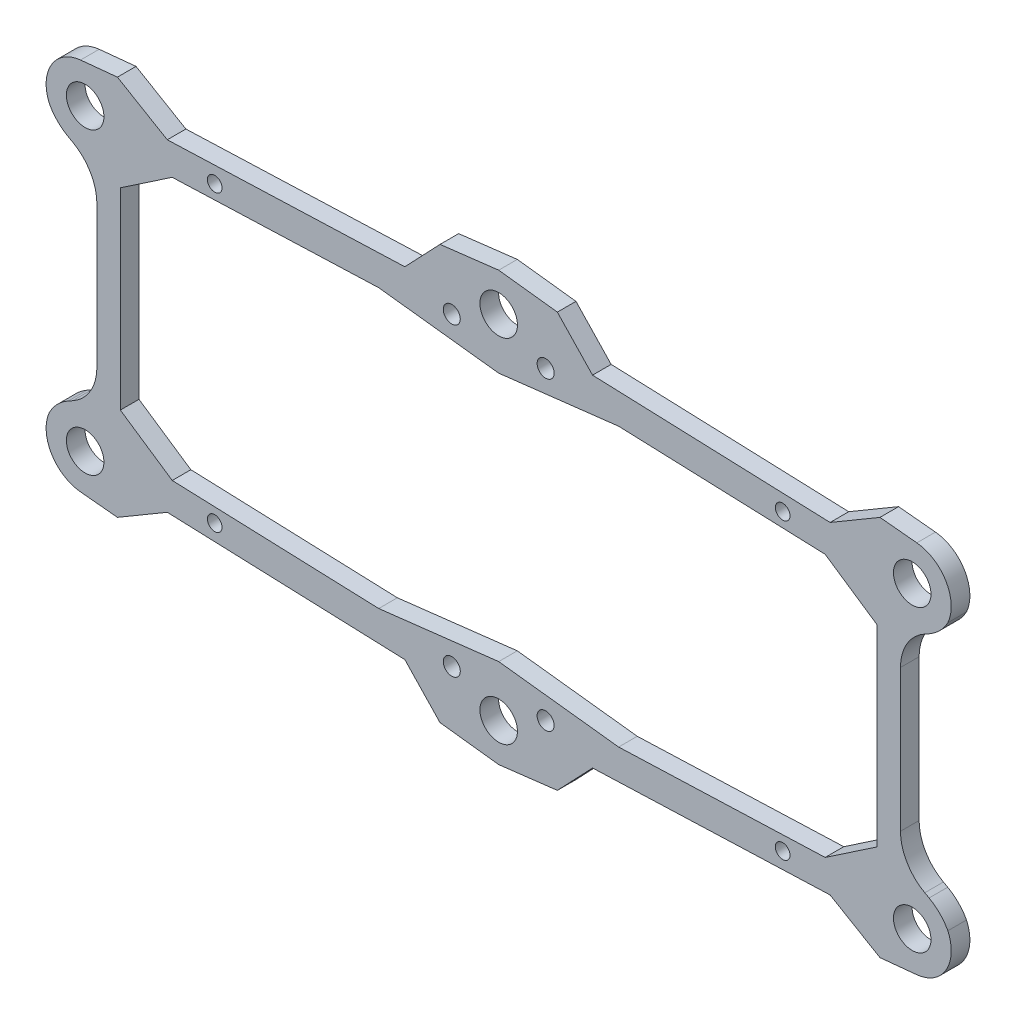
SolidWorks part; units mm, degrees
material "AISI 304"
ref_plane "Front Plane" through (0, 0, 0) normal (0, 0, 1) x (1, 0, 0)
ref_plane "Top Plane" through (0, 0, 0) normal (0, 1, 0) x (1, 0, 0)
ref_plane "Right Plane" through (0, 0, 0) normal (1, 0, 0) x (0, 0, -1)
sketch "Sketch1" plane through (0, 0, 0) normal (0, 0, 1) x (1, 0, 0)
  line L0 (0, 36.5) -> (-10, 35.3071)
  line L1 (-10, 35.3071) -> (-16, 29)
  line L2 (-16, 29) -> (-56.5, 27.5)
  line L3 (-56.5, 27.5) -> (-76.5, 14)
  line L4 (-76.5, 14) -> (-76.5, -14)
  line L5 (-87.0431, 0) -> (20.0163, 0) construction
  line L6 (0, 32.2788) -> (0, 0) construction
  line L7 (76.5, 14) -> (76.5, -14)
  line L8 (56.5, 27.5) -> (76.5, 14)
  line L9 (16, 29) -> (56.5, 27.5)
  line L10 (10, 35.3071) -> (16, 29)
  line L11 (0, 36.5) -> (10, 35.3071)
  line L12 (0, -36.5) -> (10, -35.3071)
  line L13 (10, -35.3071) -> (16, -29)
  line L14 (16, -29) -> (56.5, -27.5)
  line L15 (56.5, -27.5) -> (76.5, -14)
  line L16 (-56.5, -27.5) -> (-76.5, -14)
  line L17 (-16, -29) -> (-56.5, -27.5)
  line L18 (-10, -35.3071) -> (-16, -29)
  line L19 (0, -36.5) -> (-10, -35.3071)
  circle A0 centre (0, 30) radius 3.2
  circle A1 centre (-50, 0) radius 19.5 construction
  circle A2 centre (50, 0) radius 19.5 construction
  circle A3 centre (0, -30) radius 3.2
  point P35 (76.5, 0)
  point P36 (-76.5, 0)
  dimension "D1" = 6.4
  dimension "D2" = 39
  dimension "D3" = 60
  dimension "D4" = 100
  dimension "D5" = 153
  dimension "D6" = 73
  dimension "D7" = 28
  dimension "D8" = 55
  dimension "D9" = 20
  dimension "D10" = 32
  dimension "D11" = 20
  dimension "D12" = 58
extrude "Boss-Extrude1" add sketch "Sketch1" along normal blind 3.175
sketch "Sketch3" plane through (0, 0, 3.175) normal (0, 0, 1) x (1, 0, 0)
  line L0 (-56.5, 27.5) -> (-65, 32.5)
  line L1 (-56.5, 27.5) -> (-76.5, 14) construction
  line L2 (-65, 32.5) -> (-80.3, 31)
  line L3 (-80.3, 31) -> (-73.537, 16)
  line L4 (-73.537, 16) -> (-56.5, 27.5)
  line L5 (0, 0) -> (0, 46.5274) construction
  line L6 (73.537, 16) -> (56.5, 27.5)
  line L7 (80.3, 31) -> (73.537, 16)
  line L8 (65, 32.5) -> (80.3, 31)
  line L9 (56.5, 27.5) -> (65, 32.5)
  line L10 (0, 0) -> (-26.0239, 0) construction
  line L11 (56.5, -27.5) -> (65, -32.5)
  line L12 (65, -32.5) -> (80.3, -31)
  line L13 (80.3, -31) -> (73.537, -16)
  line L14 (73.537, -16) -> (56.5, -27.5)
  line L15 (-73.537, -16) -> (-56.5, -27.5)
  line L16 (-80.3, -31) -> (-73.537, -16)
  line L17 (-65, -32.5) -> (-80.3, -31)
  line L18 (-56.5, -27.5) -> (-65, -32.5)
  line L19 (-16, 29) -> (-56.5, 27.5) construction
  circle A0 centre (-70.5, 25.5) radius 3.2
  circle A1 centre (70.5, 25.5) radius 3.2
  circle A2 centre (-70.5, -25.5) radius 3.2
  circle A3 centre (70.5, -25.5) radius 3.2
  dimension "D1" = 6.4
  dimension "D2" = 70.5
  dimension "D3" = 25.5
  dimension "D4" = 62
  dimension "D5" = 65
  dimension "D6" = 65
  dimension "D7" = 80.3
  dimension "D8" = 32
extrude "Boss-Extrude2" add sketch "Sketch3" against normal up to surface (3.175 mm away) up to face at (3.2, 30, 0)
fillet "Fillet1" radius 6.5 4 edges at (-80.3, 31, 1.5875) (-80.3, -31, 1.5875) (80.3, -31, 1.5875) (80.3, 31, 1.5875)
sketch "Sketch6" plane through (0, 0, 0) normal (0, 0, -1) x (-1, 0, 0)
  circle A0 centre (8, 26) radius 1.45
  circle A1 centre (-8, 26) radius 1.45
  circle A2 centre (-8, -26) radius 1.45
  circle A3 centre (8, -26) radius 1.45
  dimension "D1" = 2.9
extrude "Cut-Extrude4" cut sketch "Sketch6" against normal through all
sketch "Sketch8" plane through (0, 0, 3.175) normal (0, 0, 1) x (1, 0, 0)
  line L0 (0, 0) -> (-91.0009, 0) construction
  line L1 (0, 0) -> (0, 46.3354) construction
  line L2 (-75.6901, 20.7753) -> (-68.5, 16.819)
  line L4 (-68.5, 16.819) -> (-68.5, -16.819)
  line L5 (-75.6901, 20.7753) -> (-83.4976, 20.7753)
  line L6 (-83.4976, 20.7753) -> (-83.4976, -20.7753)
  line L7 (-75.6901, -20.7753) -> (-83.4976, -20.7753)
  line L8 (-75.6901, -20.7753) -> (-68.5, -16.819)
  line L9 (75.6901, -20.7753) -> (68.5, -16.819)
  line L10 (75.6901, -20.7753) -> (83.4976, -20.7753)
  line L11 (83.4976, 20.7753) -> (83.4976, -20.7753)
  line L12 (75.6901, 20.7753) -> (83.4976, 20.7753)
  line L13 (68.5, 16.819) -> (68.5, -16.819)
  line L14 (75.6901, 20.7753) -> (68.5, 16.819)
  line L15 (-76.5773, 22.7431) -> (-73.537, 16) construction
  line L16 (-76.5, 14) -> (-76.5, -14) construction
  point P6 (-70.2455, 14.0433)
  point P7 (-74.8082, 18.8194)
  point P9 (68.5, 0)
  point P12 (-83.4976, 0)
  point P14 (-68.5, 0)
  point P15 (83.4976, 0)
  point P24 (-70.1428, 15.4813)
  point P25 (-75.6901, 20.7753)
  point P26 (-67.7744, 16.819)
  dimension "D1" = 8
extrude "Cut-Extrude14" cut sketch "Sketch8" against normal through all
sketch "Sketch7" plane through (0, 0, 3.175) normal (0, 0, 1) x (1, 0, 0)
  line L0 (0, 15.6961) -> (0, 0) construction
  line L1 (0, 0) -> (-17.6785, 0) construction
  line L2 (0, 21.2902) -> (-20.4496, 23.6817)
  line L12 (-20.4496, 23.6817) -> (-55.6556, 22.3777)
  line L13 (-55.6556, 22.3777) -> (-64.5, 16.4078)
  line L14 (-68.5, -16.819) -> (-68.5, 16.819) construction
  line L16 (-16, 29) -> (-56.5, 27.5) construction
  line L18 (-64.5, 16.4078) -> (-64.5, -16.4078)
  line L19 (64.5, 16.4078) -> (64.5, -16.4078)
  line L20 (55.6556, 22.3777) -> (64.5, 16.4078)
  line L21 (20.4496, 23.6817) -> (55.6556, 22.3777)
  line L22 (0, 21.2902) -> (20.4496, 23.6817)
  line L23 (0, -21.2902) -> (20.4496, -23.6817)
  line L24 (20.4496, -23.6817) -> (55.6556, -22.3777)
  line L25 (55.6556, -22.3777) -> (64.5, -16.4078)
  line L26 (-55.6556, -22.3777) -> (-64.5, -16.4078)
  line L27 (-20.4496, -23.6817) -> (-55.6556, -22.3777)
  line L28 (0, -21.2902) -> (-20.4496, -23.6817)
  point P16 (64.5, 0)
  point P17 (-64.5, 0)
  point P21 (-67.513, 17.1585)
  point P22 (0, 21.2902)
  dimension "D1" = 5.15
  dimension "D2" = 4
extrude "Cut-Extrude13" cut sketch "Sketch7" against normal through all
fillet "Fillet2" radius 8 8 edges at (68.5, 16.819, 1.5875) (68.5, -16.819, 1.5875) (-68.5, -16.819, 1.5875) (-68.5, 16.819, 1.5875) (75.6901, 20.7753, 1.5875) (75.6901, -20.7753, 1.5875) (-75.6901, -20.7753, 1.5875) (-75.6901, 20.7753, 1.5875)
sketch "Sketch9" plane through (0, 0, 3.175) normal (0, 0, 1) x (1, 0, 0)
  line L0 (0, 17.6341) -> (0, 0) construction
  line L1 (0, 0) -> (-18.3275, 0) construction
  circle A0 centre (-48.4118, 25.0545) radius 1.25
  circle A1 centre (48.4118, 25.0545) radius 1.25
  circle A2 centre (-48.4118, -25.0545) radius 1.25
  circle A3 centre (48.4118, -25.0545) radius 1.25
  dimension "D1" = 2.5
extrude "Cut-Extrude15" cut sketch "Sketch9" against normal through all
